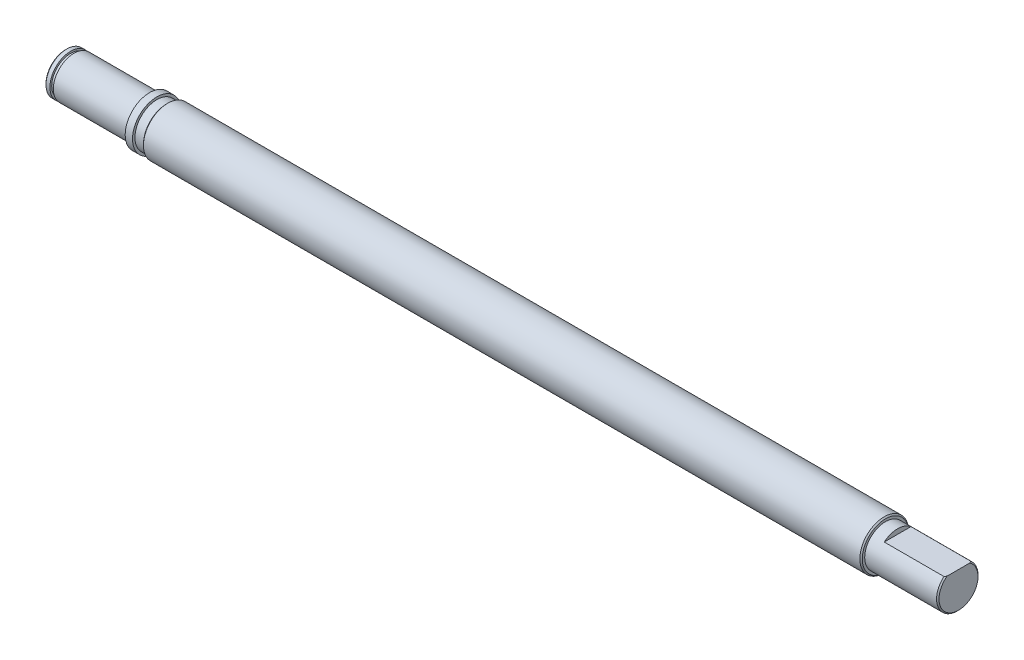
SolidWorks part; units mm, degrees
material "Сталь 45 ГОСТ 1050-88"
ref_plane "Спереди" through (0, 0, 0) normal (0, 0, 1) x (1, 0, 0)
ref_plane "Сверху" through (0, 0, 0) normal (0, 1, 0) x (1, 0, 0)
ref_plane "Справа" through (0, 0, 0) normal (1, 0, 0) x (0, 0, -1)
ref_axis "ОсьX" through (-88.99, 0, 0) along (1, 0, 0)
ref_axis "ОсьZ" through (0, 55, 0) along (0, -1, 0)
ref_axis "ОсьY" through (0, 0, -88.99) along (0, 0, 1)
sketch "Эскиз1" plane through (0, 0, 0) normal (0, 0, 1) x (1, 0, 0)
  line L0 (-850.2095, 0) -> (204.1233, 0) construction
  line L1 (0, 0) -> (0, 8.5)
  line L2 (0, 8.5) -> (-30, 8.5)
  line L3 (-30, 8.5) -> (-30, 10)
  line L4 (-30, 10) -> (-324.9983, 10)
  line L5 (-328.9983, 9) -> (-328.9983, 10)
  line L6 (-331.9983, 8.5) -> (-362.9983, 8.5)
  line L7 (-366.4983, 8.5) -> (-366.4983, 0)
  line L8 (-366.4983, 0) -> (0, 0)
  line L9 (-328.9983, 10) -> (-331.9983, 10)
  line L10 (-331.9983, 10) -> (-331.9983, 8.5)
  line L11 (-324.9983, 10) -> (-324.9983, 9)
  line L12 (-324.9983, 9) -> (-328.9983, 9)
  line L13 (-364.3983, 8.5) -> (-364.3983, 7.75)
  line L14 (-364.3983, 7.75) -> (-362.9983, 7.75)
  line L15 (-362.9983, 7.75) -> (-362.9983, 8.5)
  line L16 (-364.3983, 8.5) -> (-366.4983, 8.5)
  dimension "D1" = 17
  dimension "D2" = 20
  dimension "D3" = 17
  dimension "D4" = 30
  dimension "D5" = 18
  dimension "D6" = 299
  dimension "D7" = 4
  dimension "D8" = 3
  dimension "D9" = 20
  dimension "D10" = 31
  dimension "D11" = 15.5
  dimension "D12" = 1.4
  dimension "D13" = 2.1
revolve "Повернуть1" add sketch "Эскиз1" angle 360 mid plane about L0
cosmetic thread "Условное изображение резьбы1" parameters "D2"=17.294
chamfer "Фаска1" distance 0.5 angle 45 4 edges at (-30, 0, 10) (0, 0, 8.5) (-324.9983, 0, 10) (-366.4983, 0, 8.5)
sketch "Эскиз2" plane through (0, 0, 0) normal (1, 0, 0) x (0, 0, -1)
  line L0 (-5.4772, 6.5) -> (5.4772, 6.5)
  circle A0 centre (0, 0) radius 8.5 construction
  circle A1 centre (0, 0) radius 8.5 construction
  arc A2 (5.4772, 6.5) -> (-5.4772, 6.5) centre (0, 0) ccw
  dimension "D1" = 15
extrude "Вырез-Вытянуть1" cut sketch "Эскиз2" against normal blind 25
